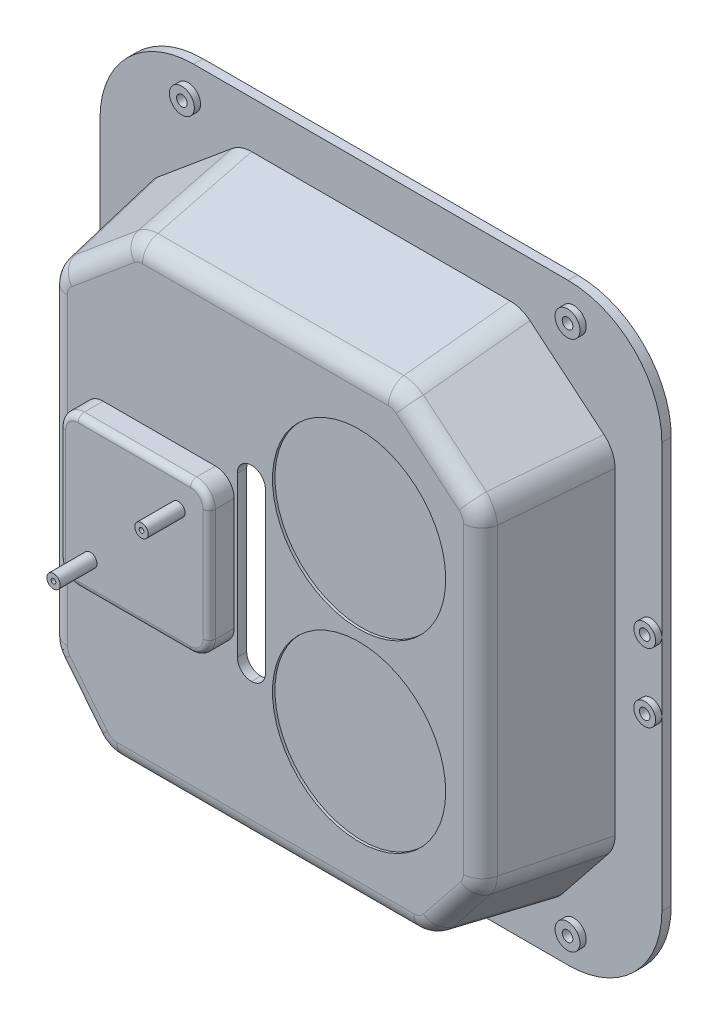
SolidWorks part; units mm, degrees
ref_plane "Front Plane" through (0, 0, 0) normal (0, 0, 1) x (1, 0, 0)
ref_plane "Top Plane" through (0, 0, 0) normal (0, 1, 0) x (1, 0, 0)
ref_plane "Right Plane" through (0, 0, 0) normal (1, 0, 0) x (0, 0, -1)
sketch "SK_Brim_180x190" plane through (0, 0, 0) normal (0, 0, 1) x (1, 0, 0)
  line L1 (-90, -95) -> (90, -95)
  line L2 (-90, -95) -> (-90, 95)
  line L3 (-90, 95) -> (90, 95)
  line L4 (90, -95) -> (90, 95)
  line L5 (-72, -77) -> (72, -77)
  line L6 (-72, -77) -> (-72, 77)
  line L7 (-72, 77) -> (72, 77)
  line L8 (72, -77) -> (72, 77)
extrude "Board_Mount_Brim_3mm" add sketch "SK_Brim_180x190" along normal blind 3
fillet "Brim_Outer_R30" radius 30 4 edges at (-90, 95, 1.5) (90, 95, 1.5) (90, -95, 1.5) (-90, -95, 1.5)
fillet "Brim_Inner_R10" radius 10 4 edges at (-72, 77, 1.5) (72, 77, 1.5) (72, -77, 1.5) (-72, -77, 1.5)
sketch "SK_Cockpit_Octagon" plane through (0, 0, 3) normal (0, 0, 1) x (1, 0, 0)
  line L0 (-55, -80) -> (55, -80)
  line L1 (55, -80) -> (75, -55)
  line L2 (75, -55) -> (75, 55)
  line L3 (75, 55) -> (45, 80)
  line L4 (45, 80) -> (-45, 80)
  line L5 (-45, 80) -> (-75, 55)
  line L6 (-75, 55) -> (-75, -55)
  line L7 (-75, -55) -> (-55, -80)
extrude "Cockpit_Canopy_37H_Draft10deg" add sketch "SK_Cockpit_Octagon" along normal blind 37 draft 10
fillet "Canopy_Corners_R10" radius 10 8 edges at (-71.738, -53.8557, 21.5) (-71.738, 53.4721, 21.5) (-43.819, 76.738, 21.5) (43.819, 76.738, 21.5) (71.738, 53.4721, 21.5) (71.738, -53.8557, 21.5) (53.4322, -76.738, 21.5) (-53.4322, -76.738, 21.5)
fillet "Canopy_Roof_R6" radius 6 16 edges at (-60.5695, -62.5944, 40) (0, -73.4759, 40) (60.5695, -62.5944, 40) (68.4759, -0.9626, 40) (55.1547, 63.0453, 40) (0, 73.4759, 40) (-55.1547, 63.0453, 40) (-68.4759, -0.9626, 40) (-51.398, -72.5055, 40) (51.398, -72.5055, 40) (67.9212, -52.5169, 40) (67.5476, 51.5095, 40) (42.4252, 72.8883, 40) (-42.4252, 72.8883, 40) (-67.5476, 51.5095, 40) (-67.9212, -52.5169, 40)
sketch "SK_Symmetric_Cavity" plane through (0, 0, 0) normal (0, 0, -1) x (-1, 0, 0)
  line L0 (-53, -77) -> (53, -77)
  line L1 (57.3444, -77) -> (-57.3444, -77) construction
  line L2 (53, -77) -> (72, -52)
  line L3 (72, 57.4649) -> (72, -58.75) construction
  line L4 (72, -52) -> (72, 52)
  line L5 (72, 52) -> (43, 77)
  line L6 (-62, 77) -> (62, 77) construction
  line L7 (43, 77) -> (-43, 77)
  line L8 (-43, 77) -> (-72, 52)
  line L9 (-72, -67) -> (-72, 67) construction
  line L10 (-72, 52) -> (-72, -52)
  line L11 (-72, -52) -> (-53, -77)
extrude "Symmetric_Electronics_Cavity_37H" cut sketch "SK_Symmetric_Cavity" against normal blind 37 draft 10
sketch "Sketch14" plane through (0, 0, 40) normal (0, 0, 1) x (1, 0, 0)
  line L1 (-58, -24) -> (-10, -24)
  line L2 (-58, -24) -> (-58, 24)
  line L3 (-58, 24) -> (-10, 24)
  line L4 (-10, -24) -> (-10, 24)
extrude "Boss-Extrude5" add sketch "Sketch14" along normal blind 8
fillet "Fillet3" radius 6 4 edges at (-58, 24, 44) (-10, 24, 44) (-10, -24, 44) (-58, -24, 44)
fillet "Fillet4" radius 2 8 edges at (-58, 0, 48) (-34, -24, 48) (-10, 0, 48) (-34, 24, 48) (-56.2426, -22.2426, 48) (-11.7574, -22.2426, 48) (-11.7574, 22.2426, 48) (-56.2426, 22.2426, 48)
sketch "Sketch15" plane through (0, 0, 48) normal (0, 0, 1) x (1, 0, 0)
  circle A0 centre (-48.1, -14.1) radius 2.15
  circle A1 centre (-19.9, 14.1) radius 2.15
extrude "Boss-Extrude6" add sketch "Sketch15" along normal blind 11.8
sketch "Sketch16" plane through (0, 0, 59.8) normal (0, 0, 1) x (1, 0, 0)
  circle A0 centre (-48.1, -14.1) radius 0.75
  circle A1 centre (-19.9, 14.1) radius 0.75
extrude "Cut-Extrude10" cut sketch "Sketch16" against normal blind 11.3
sketch "Sketch19" plane through (0, 0, 0) normal (0, 0, 1) x (1, 0, 0)
  line L0 (-50, -73) -> (50, -73)
  line L1 (-72, -77) -> (72, -77)
  line L2 (-72, -77) -> (-72, 77)
  line L3 (-72, 77) -> (72, 77)
  line L4 (72, -77) -> (72, 77)
  line L5 (50, -73) -> (68, -50)
  line L6 (68, -50) -> (68, 50)
  line L7 (68, 50) -> (40, 73)
  line L8 (40, 73) -> (-40, 73)
  line L9 (-40, 73) -> (-68, 50)
  line L10 (-68, 50) -> (-68, -50)
  line L11 (-68, -50) -> (-50, -73)
extrude "Boss-Extrude7" add sketch "Sketch19" along normal blind 3
sketch "Sketch20" plane through (0, 0, 3) normal (0, 0, 1) x (1, 0, 0)
  circle A0 centre (-86.5, -11) radius 1.7
  circle A1 centre (-86.5, 11) radius 1.7
  circle A2 centre (86.5, -11) radius 1.7
  circle A3 centre (86.5, 11) radius 1.7
  circle A4 centre (-61.7761, -84.9997) radius 1.7
  circle A5 centre (61.7761, -84.9997) radius 1.7
  circle A6 centre (-61.7761, 84.9997) radius 1.7
  circle A7 centre (61.7761, 84.9997) radius 1.7
extrude "Cut-Extrude13" cut sketch "Sketch20" against normal blind 3.2
sketch "Sketch21" plane through (0, 0, 40) normal (0, 0, 1) x (1, 0, 0)
  circle A0 centre (30, -29.5) radius 27.75
extrude "Cut-Extrude14" cut sketch "Sketch21" against normal blind 0.8
sketch "Sketch22" plane through (0, 0, 40) normal (0, 0, 1) x (1, 0, 0)
  circle A0 centre (30, 29.5) radius 27.75
extrude "Cut-Extrude15" cut sketch "Sketch22" against normal blind 0.8
sketch "Sketch24" plane through (0, 0, 40) normal (0, 0, 1) x (1, 0, 0)
  line L1 (-9, -30) -> (0, -30)
  line L2 (-9, -30) -> (-9, 30)
  line L3 (-9, 30) -> (0, 30)
  line L4 (0, -30) -> (0, 30)
extrude "Cut-Extrude18" cut sketch "Sketch24" against normal blind 4
fillet "Fillet5" radius 4.5 4 edges at (-9, -30, 38.5) (0, -30, 38.5) (0, 30, 38.5) (-9, 30, 38.5)
sketch "Sketch25" plane through (0, 0, 3) normal (0, 0, 1) x (1, 0, 0)
  circle A0 centre (-86.5, -11) radius 4
  circle A1 centre (-86.5, -11) radius 1.7
  circle A2 centre (-86.5, 11) radius 4
  circle A3 centre (-86.5, 11) radius 1.7
  circle A4 centre (86.5, -11) radius 3.5
  circle A5 centre (86.5, -11) radius 1.7
  circle A6 centre (86.5, 11) radius 3.5
  circle A7 centre (86.5, 11) radius 1.7
  circle A8 centre (-61.7761, -84.9997) radius 4
  circle A9 centre (-61.7761, -84.9997) radius 1.7
  circle A10 centre (61.7761, -84.9997) radius 4
  circle A11 centre (61.7761, -84.9997) radius 1.7
  circle A12 centre (-61.7761, 84.9997) radius 4
  circle A13 centre (-61.7761, 84.9997) radius 1.7
  circle A14 centre (61.7761, 84.9997) radius 4
  circle A15 centre (61.7761, 84.9997) radius 1.7
extrude "Boss-Extrude8" add sketch "Sketch25" along normal blind 2
